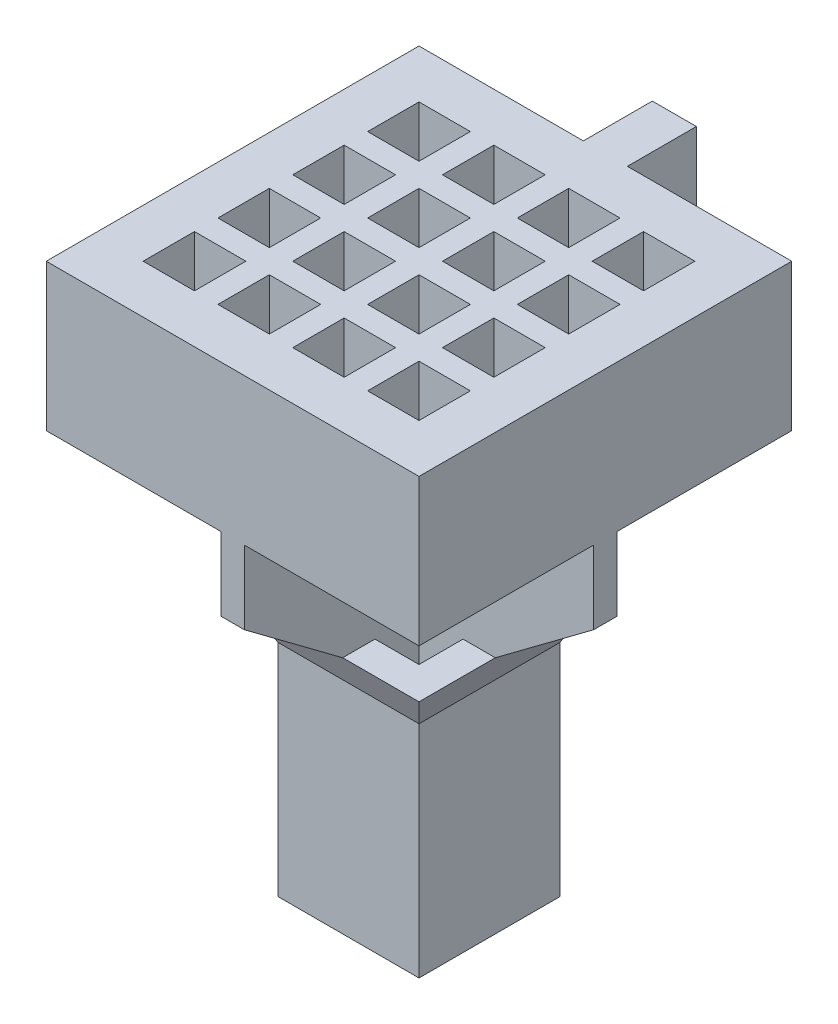
SolidWorks part; units mm, degrees
note: The reader was unsure of these and kept them because the rebuilt part matched: shared geometry of "Sketch7<3>", "Sketch9<2>".
ref_plane "Front Plane" through (0, 0, 0) normal (0, 0, 1) x (1, 0, 0)
ref_plane "Top Plane" through (0, 0, 0) normal (0, 1, 0) x (1, 0, 0)
ref_plane "Right Plane" through (0, 0, 0) normal (1, 0, 0) x (0, 0, -1)
sketch "top_panel" plane through (0, 0, 0) normal (0, 1, 0) x (1, 0, 0)
  line L1 (-18.4144, 13.6444) -> (-15.8744, 13.6444)
  line L2 (-18.4144, 13.6444) -> (-18.4144, 11.1044)
  line L3 (-18.4144, 11.1044) -> (-15.8744, 11.1044)
  line L4 (-15.8744, 13.6444) -> (-15.8744, 11.1044)
  dimension "D1" = 2.54
  dimension "D2" = 2.54
extrude "Boss-Extrude1" add sketch "top_panel" against normal blind 1
sketch "well_holes" plane through (0, 0, 0) normal (0, 1, 0) x (1, 0, 0)
  line L0 (-17.5744, 13.3144) -> (-17.2244, 13.3144)
  line L1 (-18.0844, 13.3144) -> (-17.7344, 13.3144)
  line L2 (-18.0844, 13.3144) -> (-18.0844, 12.9644)
  line L3 (-18.0844, 12.9644) -> (-17.7344, 12.9644)
  line L4 (-17.7344, 13.3144) -> (-17.7344, 12.9644)
  line L5 (-17.2244, 13.3144) -> (-17.2244, 12.9644)
  line L6 (-17.5744, 12.9644) -> (-17.2244, 12.9644)
  line L7 (-17.5744, 13.3144) -> (-17.5744, 12.9644)
  line L8 (-17.0644, 13.3144) -> (-16.7144, 13.3144)
  line L9 (-16.7144, 13.3144) -> (-16.7144, 12.9644)
  line L10 (-17.0644, 12.9644) -> (-16.7144, 12.9644)
  line L11 (-17.0644, 13.3144) -> (-17.0644, 12.9644)
  line L12 (-16.5544, 13.3144) -> (-16.2044, 13.3144)
  line L13 (-16.2044, 13.3144) -> (-16.2044, 12.9644)
  line L14 (-16.5544, 12.9644) -> (-16.2044, 12.9644)
  line L15 (-16.5544, 13.3144) -> (-16.5544, 12.9644)
  line L16 (-17.5744, 12.8044) -> (-17.2244, 12.8044)
  line L17 (-17.2244, 12.8044) -> (-17.2244, 12.4544)
  line L18 (-17.5744, 12.4544) -> (-17.2244, 12.4544)
  line L19 (-17.5744, 12.8044) -> (-17.5744, 12.4544)
  line L20 (-17.0644, 12.8044) -> (-16.7144, 12.8044)
  line L21 (-16.7144, 12.8044) -> (-16.7144, 12.4544)
  line L22 (-17.0644, 12.4544) -> (-16.7144, 12.4544)
  line L23 (-17.0644, 12.8044) -> (-17.0644, 12.4544)
  line L24 (-16.5544, 12.8044) -> (-16.2044, 12.8044)
  line L25 (-16.2044, 12.8044) -> (-16.2044, 12.4544)
  line L26 (-16.5544, 12.4544) -> (-16.2044, 12.4544)
  line L27 (-16.5544, 12.8044) -> (-16.5544, 12.4544)
  line L28 (-17.5744, 12.2944) -> (-17.2244, 12.2944)
  line L29 (-17.2244, 12.2944) -> (-17.2244, 11.9444)
  line L30 (-17.5744, 11.9444) -> (-17.2244, 11.9444)
  line L31 (-17.5744, 12.2944) -> (-17.5744, 11.9444)
  line L32 (-17.0644, 12.2944) -> (-16.7144, 12.2944)
  line L33 (-16.7144, 12.2944) -> (-16.7144, 11.9444)
  line L34 (-17.0644, 11.9444) -> (-16.7144, 11.9444)
  line L35 (-17.0644, 12.2944) -> (-17.0644, 11.9444)
  line L36 (-16.5544, 12.2944) -> (-16.2044, 12.2944)
  line L37 (-16.2044, 12.2944) -> (-16.2044, 11.9444)
  line L38 (-16.5544, 11.9444) -> (-16.2044, 11.9444)
  line L39 (-16.5544, 12.2944) -> (-16.5544, 11.9444)
  line L40 (-17.5744, 11.7844) -> (-17.2244, 11.7844)
  line L41 (-17.2244, 11.7844) -> (-17.2244, 11.4344)
  line L42 (-17.5744, 11.4344) -> (-17.2244, 11.4344)
  line L43 (-17.5744, 11.7844) -> (-17.5744, 11.4344)
  line L44 (-17.0644, 11.7844) -> (-16.7144, 11.7844)
  line L45 (-16.7144, 11.7844) -> (-16.7144, 11.4344)
  line L46 (-17.0644, 11.4344) -> (-16.7144, 11.4344)
  line L47 (-17.0644, 11.7844) -> (-17.0644, 11.4344)
  line L48 (-16.5544, 11.7844) -> (-16.2044, 11.7844)
  line L49 (-16.2044, 11.7844) -> (-16.2044, 11.4344)
  line L50 (-16.5544, 11.4344) -> (-16.2044, 11.4344)
  line L51 (-16.5544, 11.7844) -> (-16.5544, 11.4344)
  line L52 (-18.0844, 12.8044) -> (-17.7344, 12.8044)
  line L53 (-17.7344, 12.8044) -> (-17.7344, 12.4544)
  line L54 (-18.0844, 12.4544) -> (-17.7344, 12.4544)
  line L55 (-18.0844, 12.8044) -> (-18.0844, 12.4544)
  line L56 (-18.0844, 12.2944) -> (-17.7344, 12.2944)
  line L57 (-17.7344, 12.2944) -> (-17.7344, 11.9444)
  line L58 (-18.0844, 11.9444) -> (-17.7344, 11.9444)
  line L59 (-18.0844, 12.2944) -> (-18.0844, 11.9444)
  line L60 (-18.0844, 11.7844) -> (-17.7344, 11.7844)
  line L61 (-17.7344, 11.7844) -> (-17.7344, 11.4344)
  line L62 (-18.0844, 11.4344) -> (-17.7344, 11.4344)
  line L63 (-18.0844, 11.7844) -> (-18.0844, 11.4344)
  line L64 (-18.4144, 13.6444) -> (-18.4144, 11.1044) construction
  line L65 (-15.8744, 13.6444) -> (-18.4144, 13.6444) construction
  dimension "D1" = 0.35
  dimension "D2" = 0.35
  dimension "D5" = 0.33
  dimension "D6" = 0.33
  dimension "D3" = 4
  dimension "D4" = 4
extrude "wells" cut sketch "well_holes" against normal blind 1
sketch "support_wall_sketch" plane through (0, -1, 0) normal (0, -1, 0) x (-1, 0, 0)
  line L6 (18.4144, 11.1044) -> (15.8744, 11.1044) construction
  line L7 (17.0644, 11.1044) -> (17.2244, 11.1044)
  line L8 (17.0644, 11.1044) -> (17.0644, 13.6444)
  line L9 (17.0644, 13.6444) -> (17.2244, 13.6444)
  line L10 (17.2244, 11.1044) -> (17.2244, 13.6444)
  line L11 (15.8744, 13.6444) -> (18.4144, 13.6444) construction
ref_plane "Plane1" through (0, -2, 0) normal (0, 1, 0) x (1, 0, 0)
sketch "Sketch4" plane through (0, -2, 0) normal (0, 1, 0) x (1, 0, 0)
  line L1 (-17.7444, 12.2944) -> (-16.5444, 12.2944)
  line L2 (-17.7444, 12.2944) -> (-17.7444, 12.4544)
  line L3 (-17.7444, 12.4544) -> (-16.5444, 12.4544)
  line L4 (-16.5444, 12.2944) -> (-16.5444, 12.4544)
  line L10 (-16.7144, 12.4544) -> (-16.7144, 12.8044) construction
  line L11 (-17.5744, 12.8044) -> (-17.5744, 12.4544) construction
  dimension "D1" = 0.17
  dimension "D2" = 0.17
sketch "Sketch5" plane through (0, -1, 0) normal (0, -1, 0) x (-1, 0, 0)
  line L0 (18.4144, 13.6444) -> (18.4144, 11.1044) construction
  line L1 (18.4144, 12.2944) -> (15.8744, 12.2944)
  line L2 (18.4144, 12.2944) -> (18.4144, 12.4544)
  line L3 (18.4144, 12.4544) -> (15.8744, 12.4544)
  line L4 (15.8744, 12.2944) -> (15.8744, 12.4544)
  line L5 (15.8744, 11.1044) -> (15.8744, 13.6444) construction
sketch "Sketch6" plane through (0, -2, 0) normal (0, 1, 0) x (1, 0, 0)
  line L1 (-17.2244, 11.9444) -> (-17.0644, 11.9444)
  line L2 (-17.2244, 11.9444) -> (-17.2244, 12.8044)
  line L3 (-17.2244, 12.8044) -> (-17.0644, 12.8044)
  line L4 (-17.0644, 11.9444) -> (-17.0644, 12.8044)
extrude "Boss-Extrude5" add sketch "Sketch5" along normal blind 0.5
loft "Loft3" add profiles "Sketch4" section face at (-17.1444, -1.5, -12.3744) section "Sketch4" connector at (-18.4144, -1.5, -12.2944) connector at (-17.7444, -2, -12.2944)
extrude "Boss-Extrude7" add sketch "support_wall_sketch" along normal blind 0.5
sketch "Sketch7" plane through (0, -2, 0) normal (0, 1, 0) x (1, 0, 0)
  line L1 (-17.0644, 12.9744) -> (-17.2244, 12.9744)
  line L2 (-17.0644, 12.9744) -> (-17.0644, 12.4544)
  line L3 (-17.0644, 12.4544) -> (-17.2244, 12.4544)
  line L4 (-17.2244, 12.9744) -> (-17.2244, 12.4544)
  line L5 (-17.0644, 11.7744) -> (-17.2244, 11.7744)
  line L6 (-17.0644, 11.7744) -> (-17.0644, 12.2944)
  line L7 (-17.0644, 12.2944) -> (-17.2244, 12.2944)
  line L8 (-17.2244, 11.7744) -> (-17.2244, 12.2944)
  dimension "D1" = 0.52
  dimension "D2" = 0.52
loft "Loft6" add section face at (-17.1444, -1.5, -11.6994) section "Sketch7" connector at (-17.0644, -1.5, -11.1044) connector at (-17.0644, -2, -11.7744)
loft "Loft7" add section face at (-17.1444, -1.5, -13.0494) section "Sketch7<3>" connector at (-17.2244, -1.5, -13.6444) connector at (-17.2244, -2, -12.9744)
sketch "Sketch7<3>" plane through (0, -2, 0) normal (0, 1, 0) x (1, 0, 0) same geometry as "Sketch7"
sketch "Sketch8" plane through (0, -2, 0) normal (0, 1, 0) x (1, 0, 0)
  line L1 (-17.7444, 11.7744) -> (-16.5444, 11.7744)
  line L2 (-17.7444, 11.7744) -> (-17.7444, 12.9744)
  line L3 (-17.7444, 12.9744) -> (-16.5444, 12.9744)
  line L4 (-16.5444, 11.7744) -> (-16.5444, 12.9744)
  line L5 (-17.0644, 12.2944) -> (-16.5444, 12.2944) construction
  line L6 (-16.5444, 12.4544) -> (-17.0644, 12.4544) construction
  line L7 (-17.0644, 11.7744) -> (-17.0644, 12.2944) construction
  dimension "D1" = 1.2
  dimension "D2" = 0.52
  dimension "D3" = 0.52
  dimension "D4" = 0.52
  dimension "D5" = 0.52
ref_plane "Plane2" through (0, -2.25, 0) normal (0, 1, 0) x (1, 0, 0)
sketch "Sketch9" plane through (0, -2.25, 0) normal (0, 1, 0) x (1, 0, 0)
  line L0 (-17.2244, 11.7744) -> (-17.2244, 12.2944) construction
  line L1 (-17.6244, 11.8944) -> (-16.6644, 11.8944)
  line L2 (-17.6244, 11.8944) -> (-17.6244, 12.8544)
  line L3 (-17.6244, 12.8544) -> (-16.6644, 12.8544)
  line L4 (-16.6644, 11.8944) -> (-16.6644, 12.8544)
  line L5 (-17.0644, 11.7744) -> (-17.0644, 12.2944) construction
  line L6 (-17.0644, 12.2944) -> (-16.5444, 12.2944) construction
  dimension "D1" = 0.96
  dimension "D2" = 0.96
  dimension "D3" = 0.4
  dimension "D4" = 0.4
  dimension "D5" = 0.4
loft "mezzanine" add profiles "Sketch8", "Sketch9" connector at (-17.7444, -2, -11.7744) connector at (-17.6244, -2.25, -11.8944)
sketch "tetrode_entry_holdes" plane through (0, -2, 0) normal (0, 1, 0) x (1, 0, 0)
  line L1 (-17.2244, 12.2944) -> (-17.5244, 12.2944)
  line L2 (-17.2244, 12.2944) -> (-17.2244, 11.9944)
  line L3 (-17.2244, 11.9944) -> (-17.5244, 11.9944)
  line L4 (-17.5244, 12.2944) -> (-17.5244, 11.9944)
  line L5 (-16.7644, 11.9944) -> (-17.0644, 11.9944)
  line L6 (-16.7644, 12.2944) -> (-16.7644, 11.9944)
  line L7 (-16.7644, 12.2944) -> (-17.0644, 12.2944)
  line L8 (-17.0644, 12.2944) -> (-17.0644, 11.9944)
  line L9 (-16.7644, 12.4544) -> (-17.0644, 12.4544)
  line L10 (-16.7644, 12.7544) -> (-16.7644, 12.4544)
  line L11 (-16.7644, 12.7544) -> (-17.0644, 12.7544)
  line L12 (-17.0644, 12.7544) -> (-17.0644, 12.4544)
  line L13 (-17.2244, 12.4544) -> (-17.5244, 12.4544)
  line L14 (-17.2244, 12.7544) -> (-17.2244, 12.4544)
  line L15 (-17.2244, 12.7544) -> (-17.5244, 12.7544)
  line L16 (-17.5244, 12.7544) -> (-17.5244, 12.4544)
  dimension "D1" = 0.3
  dimension "D2" = 0.3
  dimension "D3" = 2
  dimension "D4" = 2
extrude "tetrode_guide" add sketch "Sketch9<2>" against normal blind 1.5
sketch "Sketch9<2>" plane through (0, -2.25, 0) normal (0, 1, 0) x (1, 0, 0) same geometry as "Sketch9"
extrude "tetrode_guide_holes" cut sketch "tetrode_entry_holdes" against normal blind 1.75
sketch "Sketch10" plane through (0, 0, 0) normal (0, 1, 0) x (1, 0, 0)
  line L1 (-17.2944, 13.3144) -> (-16.9944, 13.3144)
  line L2 (-17.2944, 13.3144) -> (-17.2944, 14.1144)
  line L3 (-17.2944, 14.1144) -> (-16.9944, 14.1144)
  line L4 (-16.9944, 13.3144) -> (-16.9944, 14.1144)
  line L10 (-17.0644, 13.3144) -> (-17.0644, 12.9644) construction
  dimension "D1" = 0.8
  dimension "D3" = 0.3
  dimension "D4" = 0.07
extrude "tab" add sketch "Sketch10" against normal blind 1
